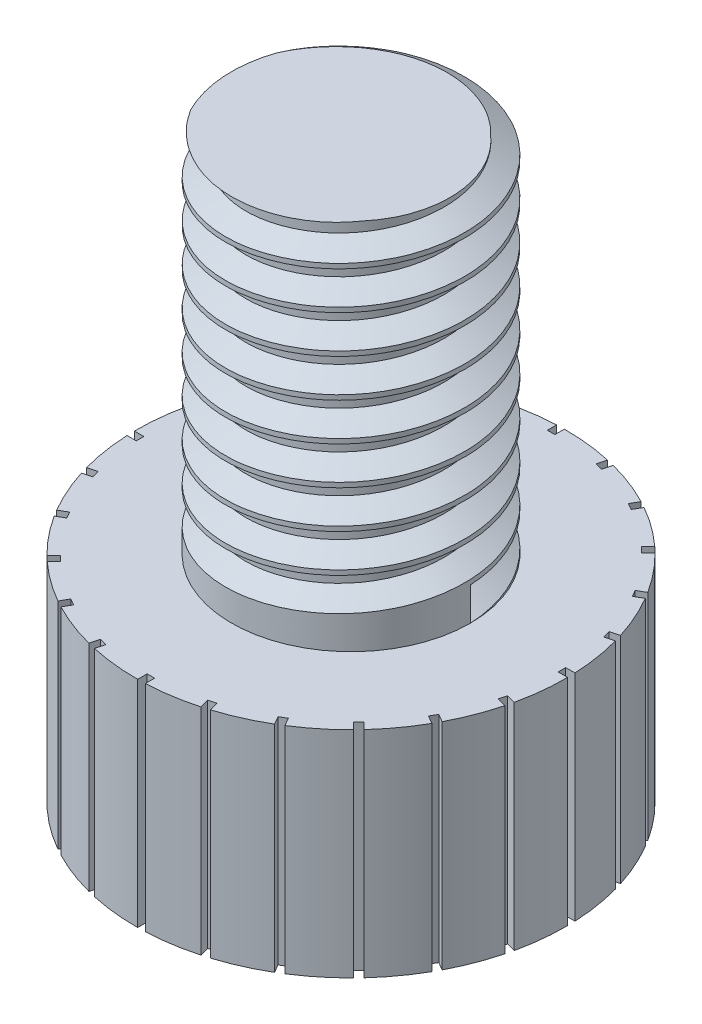
SolidWorks part; units mm, degrees
ref_plane "前视基准面" through (0, 0, 0) normal (0, 0, 1) x (1, 0, 0)
ref_plane "上视基准面" through (0, 0, 0) normal (0, 1, 0) x (1, 0, 0)
ref_plane "右视基准面" through (0, 0, 0) normal (1, 0, 0) x (0, 0, -1)
sketch "草图1" plane through (0, 0, 0) normal (0, 1, 0) x (1, 0, 0)
  circle A0 centre (0, 0) radius 1.8
  dimension "D1" = 3.6
extrude "凸台-拉伸1" add sketch "草图1" along normal blind 1.8
sketch "草图2" plane through (0, 1.8, 0) normal (0, 1, 0) x (1, 0, 0)
  circle A0 centre (0, 0) radius 1
  dimension "D1" = 2
extrude "凸台-拉伸2" add sketch "草图2" along normal blind 3
thread "螺纹线1" pitch 0.3175 method cut profile "螺纹线轮廓2" start angle 0, offset 0, length 6, pitch 0.3175, diameter 2
ref_plane "基准面2" through (1, 1.8, 0) normal (0, 0, 1) x (1, 0, 0)
sketch "螺纹线轮廓2" plane through (1, 1.8, 0) normal (0, 0, 1) x (1, 0, 0)
  line L0 (0, 0) -> (0, 0.3175) construction
  line L11 (0, 0) -> (0, 0.2778)
  line L12 (0, 0.2778) -> (-0.1719, 0.1786)
  line L13 (-0.1719, 0.1786) -> (-0.1719, 0.0992)
  line L15 (-0.1719, 0.0992) -> (0, 0)
  line L17 (-0.1719, 0.1389) -> (0, 0.1389) construction
  point P2 (0, 0)
  dimension "Pitch" = 0.3175
  dimension "Profile_Angle" = 60
  dimension "Profile_Land" = 0.0794
  dimension "Profile_Height" = 0.1719
sketch "草图7" plane through (0, 0, 0) normal (0, -1, 0) x (-1, 0, 0)
  line L1 (-0.866, 0) -> (-0.433, -0.75)
  line L2 (-0.433, -0.75) -> (0.433, -0.75)
  line L3 (0.433, -0.75) -> (0.866, 0)
  line L4 (0.866, 0) -> (0.433, 0.75)
  line L5 (0.433, 0.75) -> (-0.433, 0.75)
  line L6 (-0.433, 0.75) -> (-0.866, 0)
  circle A0 centre (0, 0) radius 0.75 construction
  dimension "D1" = 1.5
extrude "切除-拉伸1" cut sketch "草图7" against normal blind 1
sketch "草图8" plane through (0, 0, 0) normal (0, -1, 0) x (-1, 0, 0)
  line L4 (0.0138, 1.7208) -> (0.0768, 1.7208)
  line L5 (0.0138, 1.7208) -> (0.0138, 1.9428)
  line L6 (0.0138, 1.9428) -> (0.0768, 1.9428)
  line L7 (0.0768, 1.7208) -> (0.0768, 1.9428)
extrude "切除-拉伸2" cut sketch "草图8" against normal blind 2
sketch "草图10" plane through (0, 0, 0) normal (0, 0, 1) x (1, 0, 0)
  line L0 (0, -0.405) -> (0, 2.0875) construction
pattern_circular "阵列(圆周)2" count 24 over 360 about axis through (0, -0.405, 0) along (0, 1, 0) of "切除-拉伸2" reverse direction yes
